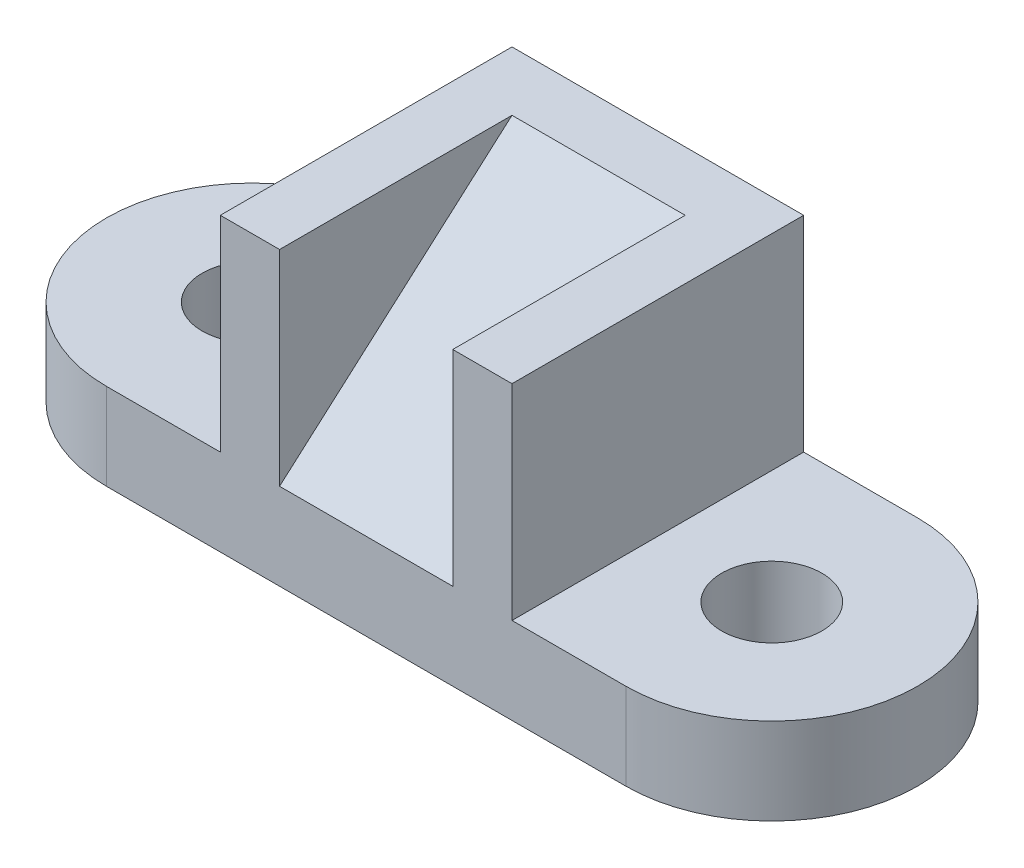
SolidWorks part; units mm, degrees
ref_plane "Front Plane" through (0, 0, 0) normal (0, 0, 1) x (1, 0, 0)
ref_plane "Top Plane" through (0, 0, 0) normal (0, 1, 0) x (1, 0, 0)
ref_plane "Right Plane" through (0, 0, 0) normal (1, 0, 0) x (0, 0, -1)
sketch "Sketch1" plane through (0, 0, 0) normal (0, 1, 0) x (1, 0, 0)
  line L0 (-57, 0) -> (57, 0) construction
  line L1 (-57, 32) -> (57, 32)
  line L2 (-57, -32) -> (57, -32)
  arc A0 (-57, 32) -> (-57, -32) centre (-57, 0) ccw
  arc A1 (57, -32) -> (57, 32) centre (57, 0) ccw
  point P3 (0, 0)
  point P8 (0, 0)
  dimension "D2" = 32
  dimension "D1" = 114
extrude "Boss-Extrude1" add sketch "Sketch1" along normal blind 19
sketch "Sketch8" plane through (0, 19, 0) normal (0, 1, 0) x (1, 0, 0)
  circle A0 centre (-57, 0) radius 11
  circle A1 centre (57, 0) radius 11
  dimension "D1" = 22
extrude "Cut-Extrude12" cut sketch "Sketch8" against normal mid plane 38
sketch "Sketch9" plane through (0, 0, 0) normal (1, 0, 0) x (0, 0, -1)
  line L0 (-32, 0) -> (32, 0) construction
  line L5 (-32, 64) -> (32, 64)
  line L6 (-32, 64) -> (-32, 0)
  line L7 (-32, 0) -> (32, 0)
  line L8 (32, 64) -> (32, 0)
  line L9 (-32, 19) -> (-32, 0) construction
  line L10 (32, 19) -> (32, 0) construction
  dimension "D1" = 64
extrude "Boss-Extrude3" add sketch "Sketch9" along normal blind 32 and the other way blind 32
sketch "Sketch10" plane through (0, 0, 0) normal (1, 0, 0) x (0, 0, -1)
  line L0 (-32, 19) -> (19, 64)
  line L1 (32, 64) -> (-32, 64) construction
  line L2 (19, 64) -> (-32, 64)
  line L3 (-32, 64) -> (-32, 19)
  dimension "D1" = 51
extrude "Cut-Extrude13" cut sketch "Sketch10" against normal mid plane 38
